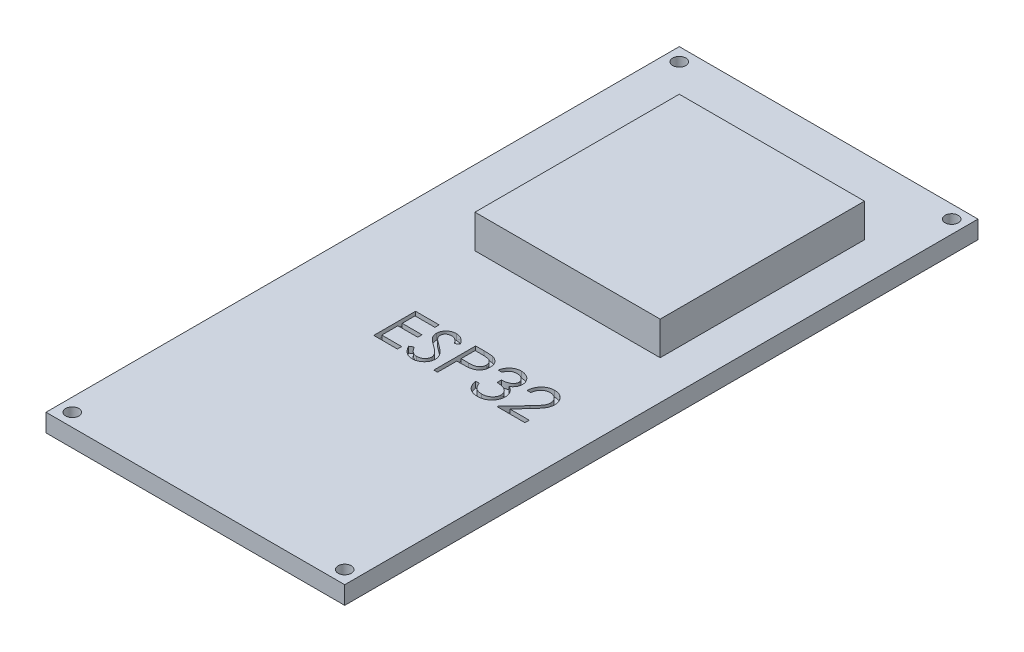
SolidWorks part; units mm, degrees
ref_plane "Front Plane" through (0, 0, 0) normal (0, 0, 1) x (1, 0, 0)
ref_plane "Top Plane" through (0, 0, 0) normal (0, 1, 0) x (1, 0, 0)
ref_plane "Right Plane" through (0, 0, 0) normal (1, 0, 0) x (0, 0, -1)
sketch "Sketch2" plane through (0, 0, 0) normal (0, 1, 0) x (1, 0, 0)
  line L1 (0, 0) -> (25, 0)
  line L2 (0, 0) -> (0, 53)
  line L3 (0, 53) -> (25, 53)
  line L4 (25, 0) -> (25, 53)
  dimension "D1" = 25
  dimension "D2" = 53
extrude "Boss-Extrude1" add sketch "Sketch2" along normal blind 1.5
sketch "Sketch3" plane through (0, 1.5, 0) normal (0, 1, 0) x (1, 0, 0)
  line L0 (0, 53) -> (0, 0) construction
  line L1 (6.25, 46.75) -> (21.75, 46.75)
  line L2 (6.25, 46.75) -> (6.25, 29.65)
  line L3 (6.25, 29.65) -> (21.75, 29.65)
  line L4 (21.75, 46.75) -> (21.75, 29.65)
  line L5 (25, 53) -> (0, 53) construction
  dimension "D1" = 6.25
  dimension "D2" = 15.5
  dimension "D3" = 17.1
  dimension "D4" = 6.25
extrude "Boss-Extrude2" add sketch "Sketch3" along normal blind 2.8
sketch "Sketch4" plane through (0, 1.5, 0) normal (0, 1, 0) x (1, 0, 0)
  text T0 "ESP32\r\n"
extrude "Cut-Extrude1" cut sketch "Sketch4" against normal blind 0.5
sketch "Sketch5" plane through (0, 1.5, 0) normal (0, 1, 0) x (1, 0, 0)
  line L0 (25, 53) -> (0, 53) construction
  line L1 (0, 53) -> (0, 0) construction
  circle A0 centre (1.1, 51.9) radius 0.55
  dimension "D1" = 1.1
  dimension "D3" = 1.1
  dimension "D2" = 1.1
extrude "Cut-Extrude2" cut sketch "Sketch5" against normal through all
ref_plane "Plane1" through (12.5, 0, 0) normal (1, 0, 0) x (0, 0, -1)
ref_plane "Plane2" through (0, 0, -26.5) normal (0, 0, -1) x (-1, 0, 0)
mirror "Mirror2" about plane through (12.5, 0, 0) normal (1, 0, 0) of "Cut-Extrude2" second plane through (0, 0, -26.5) second plane normal (0, 0, -1)
